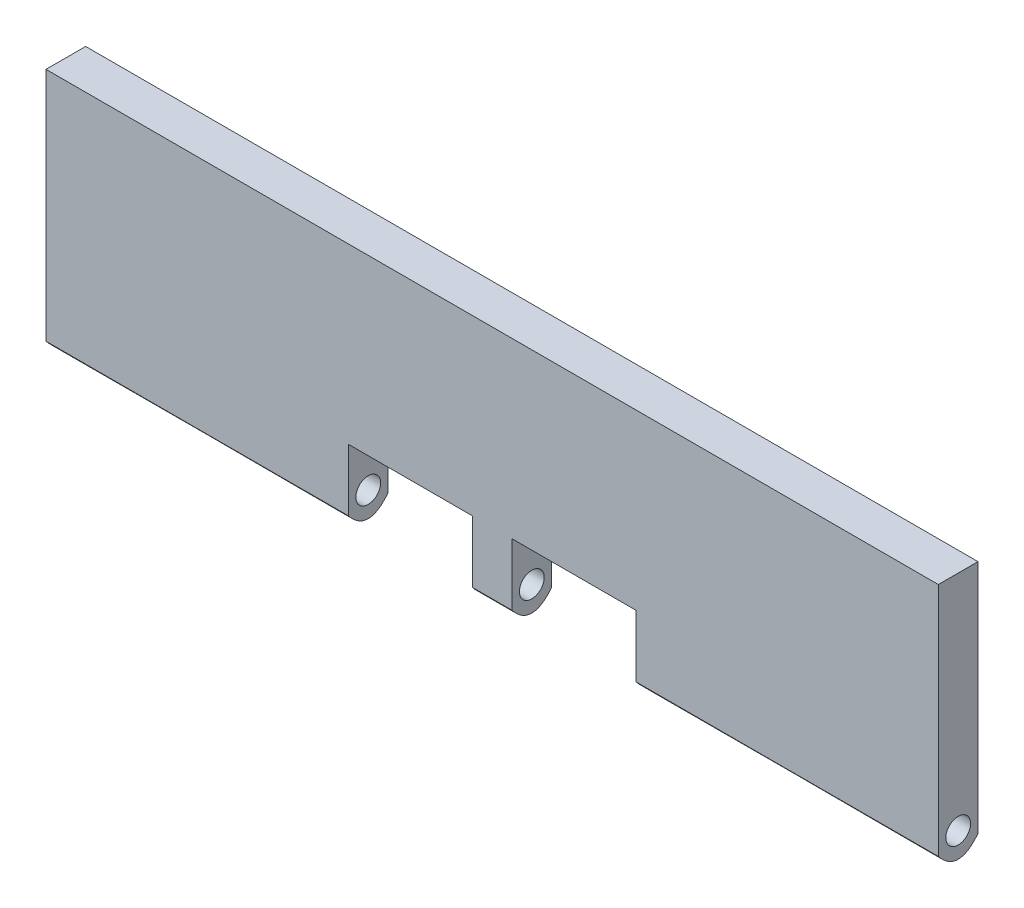
SolidWorks part; units mm, degrees
ref_plane "Plan de face" through (0, 0, 0) normal (0, 0, 1) x (1, 0, 0)
ref_plane "Plan de dessus" through (0, 0, 0) normal (0, 1, 0) x (1, 0, 0)
ref_plane "Plan de droite" through (0, 0, 0) normal (1, 0, 0) x (0, 0, -1)
sketch "Esquisse1" plane through (0, 0, 0) normal (0, 0, 1) x (1, 0, 0)
  line L0 (-29, -25) -> (-29, -10)
  line L1 (-90, -25) -> (-29, -25)
  line L2 (-90, -25) -> (-90, 25)
  line L3 (-90, 25) -> (90, 25)
  line L4 (90, -25) -> (90, 25)
  line L5 (-90, -25) -> (90, 25) construction
  line L6 (-90, 25) -> (90, -25) construction
  line L7 (-29, -10) -> (-4, -10)
  line L8 (-4, -10) -> (-4, -25)
  line L9 (0, 0) -> (0, -25) construction
  line L10 (-4, -25) -> (4, -25)
  line L11 (4, -10) -> (4, -25)
  line L12 (29, -10) -> (4, -10)
  line L13 (29, -25) -> (29, -10)
  line L14 (29, -25) -> (90, -25)
  point P0 (0, 0)
  dimension "D1" = 180
  dimension "D2" = 50
  dimension "D3" = 25
  dimension "D4" = 4
  dimension "D5" = 15
extrude "Boss.-Extru.1" add sketch "Esquisse1" along normal blind 8
sketch "Esquisse2" plane through (-90, 0, 0) normal (-1, 0, 0) x (0, 0, 1)
  line L0 (4, -25) -> (4, -8.5674) construction
  line L1 (8, -25) -> (0, -25) construction
  line L2 (4, -22.5) -> (0, -22.5) construction
  line L3 (0, 25) -> (0, -25) construction
  line L4 (8, 25) -> (8, -25) construction
  line L5 (0, -22.5) -> (0, -25)
  line L6 (0, -25) -> (8, -25)
  line L7 (8, -25) -> (8, -22.5)
  circle A0 centre (4, -20) radius 2.5
  spline S0 degree 2 poles (0, -22.5) (4, -27.5) (8, -22.5) knots 0 0 0 1 1 1
  line M1 (0, 25) -> (0, -25)
  line M2 (0, -25) -> (8, -25)
  line M3 (8, -25) -> (8, 25)
  dimension "D1" = 5
  dimension "D2" = 5
extrude "Enlèv. mat.-Extru.1" cut sketch "Esquisse2" against normal up to surface (180 mm away) contours S0 L6 M3 | S0 M1 M2 | A0 region at (-90, -24.25, 1) region at (-90, -24.25, 7) region at (-90, -20, 4) up to face at (90, 0, 4)
sketch "Esquisse4" plane through (0, 0, 0) normal (1, 0, 0) x (0, 0, -1)
  line L0 (0, 0) -> (5, 0) construction
  line L1 (5, 4.5) -> (0, 4.5)
  line L2 (0, 25) -> (0, -22.5) construction
  line L3 (5, -4.5) -> (0, -4.5)
  line L4 (0, 4.5) -> (0, -4.5)
  circle A0 centre (5, 0) radius 2.5
  arc A1 (5, -4.5) -> (5, 4.5) centre (5, 0) ccw
  dimension "D1" = 5
  dimension "D2" = 2
  dimension "D3" = 5
extrude "Boss.-Extru.2" add sketch "Esquisse4" along normal blind 2.5 and the other way blind 2.5
